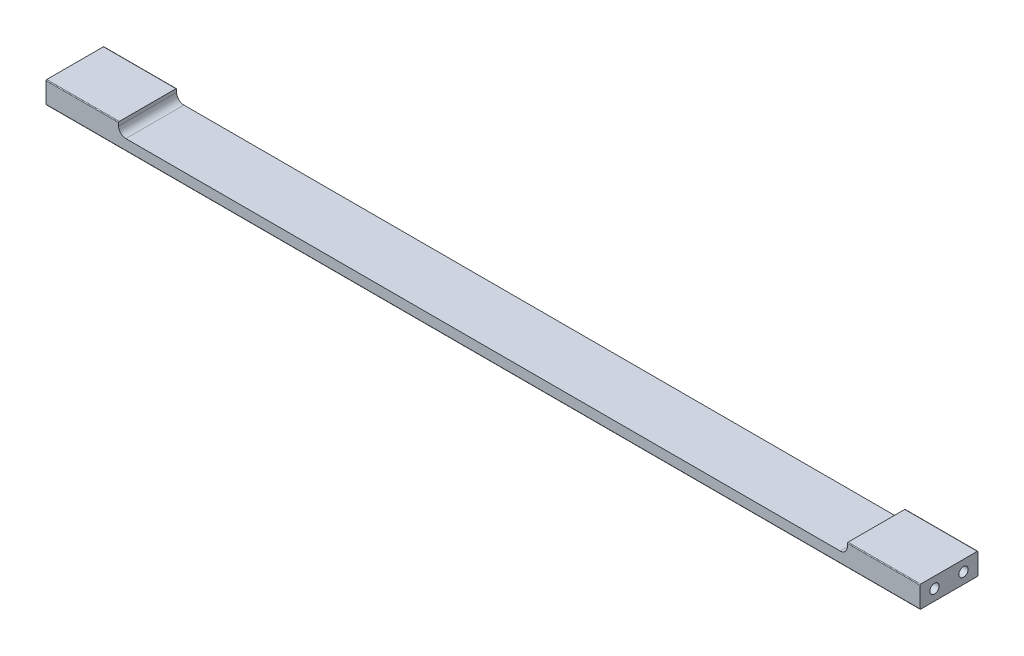
SolidWorks part; units mm, degrees
ref_plane "Front Plane" through (0, 0, 0) normal (0, 0, 1) x (1, 0, 0)
ref_plane "Top Plane" through (0, 0, 0) normal (0, 1, 0) x (1, 0, 0)
ref_plane "Right Plane" through (0, 0, 0) normal (1, 0, 0) x (0, 0, -1)
sketch "Sketch1" plane through (0, 0, 0) normal (0, 1, 0) x (1, 0, 0)
  line L1 (191.135, -12.7) -> (-191.135, -12.7)
  line L2 (191.135, -12.7) -> (191.135, 12.7)
  line L3 (191.135, 12.7) -> (-191.135, 12.7)
  line L4 (-191.135, -12.7) -> (-191.135, 12.7)
  line L5 (191.135, -12.7) -> (-191.135, 12.7) construction
  line L6 (191.135, 12.7) -> (-191.135, -12.7) construction
  point P0 (0, 0)
  dimension "Length" = 382.27
  dimension "Width" = 25.4
sketch "Sketch2" plane through (0, 0, 0) normal (1, 0, 0) x (0, 0, -1)
  line L0 (12.7, 4.7625) -> (12.7, -4.7625) construction
  point P2 (12.7, 0)
  dimension "Thickness" = 9.525
sketch "Sketch3" plane through (0, 0, 0) normal (0, 1, 0) x (1, 0, 0)
  line L1 (-191.135, 12.7) -> (191.135, 12.7)
  line L2 (-191.135, 12.7) -> (-191.135, -12.7)
  line L3 (-191.135, -12.7) -> (191.135, -12.7)
  line L4 (191.135, 12.7) -> (191.135, -12.7)
extrude "Boss-Extrude1" add sketch "Sketch3" against normal up to vertex (4.7625 mm away) and the other way up to vertex (4.7625 mm away) up to point (0, -4.7625, -12.7) other way up to point (0, 4.7625, -12.7)
fillet "Fillet1" radius 0.3143 4 edges at (0, -4.7625, 12.7) (0, -4.7625, -12.7) (0, 4.7625, -12.7) (0, 4.7625, 12.7)
sketch "Sketch4" plane through (-191.135, 0, 0) normal (-1, 0, 0) x (0, 0, 1)
  line L0 (0, 0) -> (6.35, 0) construction
  line L1 (0, 0) -> (-6.35, 0) construction
hole_wizard "Tap Drill for #10-32 Tap1" positions "Sketch5" profile "Sketch6" hole size "#10-32" standard "ANSI Inch"
sketch "Sketch5" plane through (-191.135, 0, 0) normal (-1, 0, 0) x (0, 0, 1)
  point P0 (-6.35, 0)
  point P3 (6.35, 0)
sketch "Sketch6" plane through (-191.135, 0, -6.35) normal (0, 1, 0) x (0, 0, 1)
  line L0 (0, 0) -> (0, 26.6133)
  line L1 (0, 26.6133) -> (2.0193, 25.4)
  line L2 (2.0193, 25.4) -> (2.0193, 0)
  line L5 (2.0193, 0) -> (0, 0)
  line L10 (0, 26.6133) -> (-2.0193, 25.4) construction
  line L11 (0, -6.35) -> (0, 107.95) construction
  dimension "Hole Dia." = 4.0386
  dimension "Hole Depth" = 25.4
  dimension "Drill Angle" = 118
hole_wizard "Tap Drill for #10-32 Tap2" positions "Sketch7" profile "Sketch8" hole size "#10-32" standard "ANSI Inch"
sketch "Sketch7" plane through (191.135, 0, 0) normal (1, 0, 0) x (0, 0, -1)
  point P0 (-6.35, 0)
  point P3 (6.35, 0)
sketch "Sketch8" plane through (191.135, 0, 6.35) normal (0, 1, 0) x (0, 0, -1)
  line L0 (0, 0) -> (0, 26.6133)
  line L1 (0, 26.6133) -> (2.0193, 25.4)
  line L2 (2.0193, 25.4) -> (2.0193, 0)
  line L5 (2.0193, 0) -> (0, 0)
  line L10 (0, 26.6133) -> (-2.0193, 25.4) construction
  line L11 (0, -6.35) -> (0, 107.95) construction
  dimension "Hole Dia." = 4.0386
  dimension "Hole Depth" = 25.4
  dimension "Drill Angle" = 118
sketch "Sketch9" plane through (0, 0, -12.7) normal (0, 0, -1) x (-1, 0, 0)
  line L0 (159.385, 4.7625) -> (159.385, 3.175)
  line L7 (-191.135, 4.7625) -> (191.135, 4.7625) construction
  line L8 (156.21, 0) -> (-156.21, 0)
  line L9 (-159.385, 3.175) -> (-159.385, 4.7625)
  line L10 (-159.385, 4.7625) -> (159.385, 4.7625)
  line L11 (191.135, 113.2887) -> (191.135, 38.247) construction
  line L12 (-191.135, 113.2887) -> (-191.135, 38.247) construction
  arc A0 (159.385, 3.175) -> (156.21, 0) centre (156.21, 3.175) cw
  arc A1 (-156.21, 0) -> (-159.385, 3.175) centre (-156.21, 3.175) cw
  point P15 (159.385, 0)
  point P18 (-159.385, 0)
  dimension "D4" = 3.175
  dimension "D1" = 31.75
  dimension "D2" = 31.75
  dimension "D3" = 4.7625
extrude "Cut-Extrude1" cut sketch "Sketch9" against normal through all
equation "\"D1@Fillet1\" = \"Thickness@Sketch2\" * .033"
